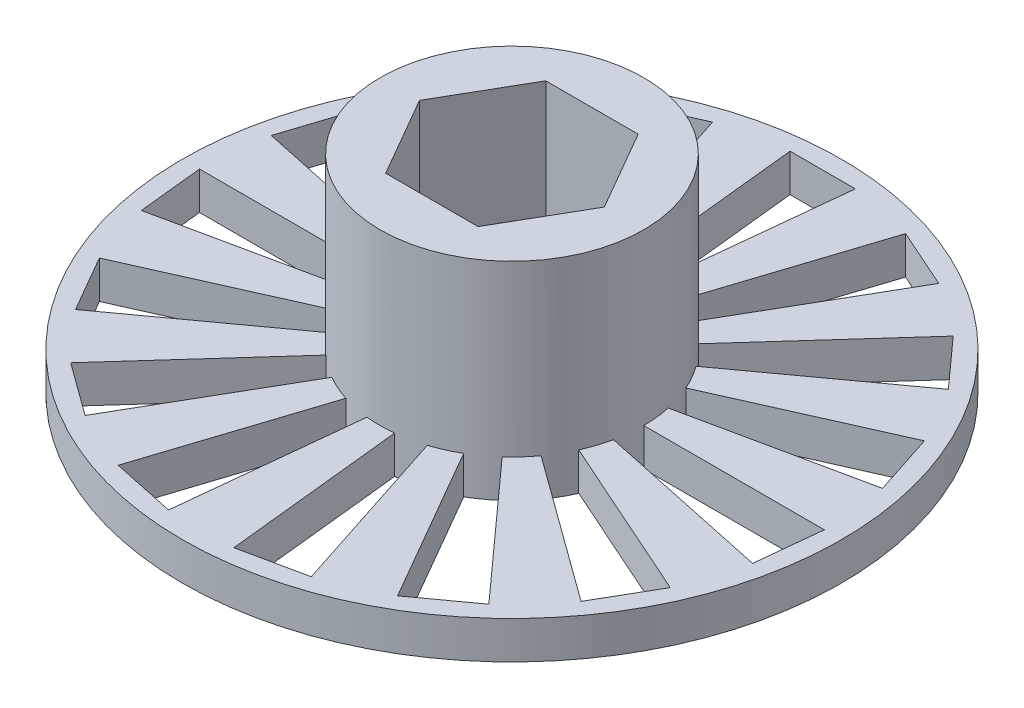
SolidWorks part; units mm, degrees
ref_plane "Front Plane" through (0, 0, 0) normal (0, 0, 1) x (1, 0, 0)
ref_plane "Top Plane" through (0, 0, 0) normal (0, 1, 0) x (1, 0, 0)
ref_plane "Right Plane" through (0, 0, 0) normal (1, 0, 0) x (0, 0, -1)
sketch "Sketch1" plane through (0, 0, 0) normal (0, 1, 0) x (1, 0, 0)
  line L0 (0, 0) -> (0, 50000) construction
  line L1 (0, 0) -> (5226.4232, 49726.0948) construction
  line L2 (0, 0) -> (-5226.4232, 49726.0948) construction
  line L3 (3.2679, 5.6602) -> (8.2954, 14.3681)
  line L4 (5.1269, 15.7789) -> (8.2954, 14.3681)
  line L5 (2.0197, 6.2159) -> (5.1269, 15.7789)
  line L6 (2.0197, 6.2159) -> (3.2679, 5.6602)
  line L7 (0.6832, 6.5) -> (1.7342, 16.5)
  line L8 (-0.6832, 6.5) -> (-1.7342, 16.5)
  line L9 (5.2876, 3.8416) -> (13.4223, 9.7519)
  line L10 (11.1015, 12.3294) -> (13.4223, 9.7519)
  line L11 (-1.7342, 16.5) -> (1.7342, 16.5)
  line L12 (-0.6832, 6.5) -> (0.6832, 6.5)
  line L13 (4.3733, 4.857) -> (11.1015, 12.3294)
  line L14 (4.3733, 4.857) -> (5.2876, 3.8416)
  line L15 (6.393, 1.3589) -> (16.2283, 3.4494)
  line L16 (15.1565, 6.7481) -> (16.2283, 3.4494)
  line L17 (5.9708, 2.6584) -> (15.1565, 6.7481)
  line L18 (5.9708, 2.6584) -> (6.393, 1.3589)
  line L19 (6.393, -1.3589) -> (16.2283, -3.4494)
  line L20 (16.5909, 0) -> (16.2283, -3.4494)
  line L21 (6.5358, 0) -> (16.5909, 0)
  line L22 (6.5358, 0) -> (6.393, -1.3589)
  line L23 (5.2876, -3.8416) -> (13.4223, -9.7519)
  line L24 (15.1565, -6.7481) -> (13.4223, -9.7519)
  line L25 (5.9708, -2.6584) -> (15.1565, -6.7481)
  line L26 (5.9708, -2.6584) -> (5.2876, -3.8416)
  line L27 (3.2679, -5.6602) -> (8.2954, -14.3681)
  line L28 (11.1015, -12.3294) -> (8.2954, -14.3681)
  line L29 (4.3733, -4.857) -> (11.1015, -12.3294)
  line L30 (4.3733, -4.857) -> (3.2679, -5.6602)
  line L31 (0.6832, -6.5) -> (1.7342, -16.5)
  line L32 (5.1269, -15.7789) -> (1.7342, -16.5)
  line L33 (2.0197, -6.2159) -> (5.1269, -15.7789)
  line L34 (2.0197, -6.2159) -> (0.6832, -6.5)
  line L35 (-2.0197, -6.2159) -> (-5.1269, -15.7789)
  line L36 (-1.7342, -16.5) -> (-5.1269, -15.7789)
  line L37 (-0.6832, -6.5) -> (-1.7342, -16.5)
  line L38 (-0.6832, -6.5) -> (-2.0197, -6.2159)
  line L39 (-4.3733, -4.857) -> (-11.1015, -12.3294)
  line L40 (-8.2954, -14.3681) -> (-11.1015, -12.3294)
  line L41 (-3.2679, -5.6602) -> (-8.2954, -14.3681)
  line L42 (-3.2679, -5.6602) -> (-4.3733, -4.857)
  line L43 (-5.9708, -2.6584) -> (-15.1565, -6.7481)
  line L44 (-13.4223, -9.7519) -> (-15.1565, -6.7481)
  line L45 (-5.2876, -3.8416) -> (-13.4223, -9.7519)
  line L46 (-5.2876, -3.8416) -> (-5.9708, -2.6584)
  line L47 (-6.5358, 0) -> (-16.5909, 0)
  line L48 (-16.2283, -3.4494) -> (-16.5909, 0)
  line L49 (-6.393, -1.3589) -> (-16.2283, -3.4494)
  line L50 (-6.393, -1.3589) -> (-6.5358, 0)
  line L51 (-5.9708, 2.6584) -> (-15.1565, 6.7481)
  line L52 (-16.2283, 3.4494) -> (-15.1565, 6.7481)
  line L53 (-6.393, 1.3589) -> (-16.2283, 3.4494)
  line L54 (-6.393, 1.3589) -> (-5.9708, 2.6584)
  line L55 (-4.3733, 4.857) -> (-11.1015, 12.3294)
  line L56 (-13.4223, 9.7519) -> (-11.1015, 12.3294)
  line L57 (-5.2876, 3.8416) -> (-13.4223, 9.7519)
  line L58 (-5.2876, 3.8416) -> (-4.3733, 4.857)
  line L59 (-2.0197, 6.2159) -> (-5.1269, 15.7789)
  line L60 (-8.2954, 14.3681) -> (-5.1269, 15.7789)
  line L61 (-3.2679, 5.6602) -> (-8.2954, 14.3681)
  line L62 (-3.2679, 5.6602) -> (-2.0197, 6.2159)
  line L64 (4.9075, 0) -> (2.4537, 4.25)
  line L65 (2.4537, 4.25) -> (-2.4537, 4.25)
  line L66 (-2.4537, 4.25) -> (-4.9075, 0)
  line L67 (-4.9075, 0) -> (-2.4537, -4.25)
  line L68 (-2.4537, -4.25) -> (2.4537, -4.25)
  line L69 (2.4537, -4.25) -> (4.9075, 0)
  circle A0 centre (0, 0) radius 17.5
  circle A1 centre (0, 0) radius 4.25 construction
  point P7 (0, 16.5)
  point P11 (0, 17.5)
  point P68 (0.0003, -0.0005)
  point P75 (0, 0)
  dimension "D1" = 35
  dimension "D2" = 6
  dimension "D3" = 6
  dimension "D4" = 6.5
  dimension "D5" = 1
  dimension "D6" = 15
  dimension "D7" = 8.5
extrude "Boss-Extrude1" add sketch "Sketch1" along normal blind 1 and the other way blind 1
sketch "Sketch2" plane through (0, 0, 0) normal (0, 1, 0) x (1, 0, 0)
  line L1 (4.9075, 0) -> (2.4537, 4.25)
  line L2 (2.4537, 4.25) -> (-2.4537, 4.25)
  line L3 (-2.4537, 4.25) -> (-4.9075, 0)
  line L4 (-4.9075, 0) -> (-2.4537, -4.25)
  line L5 (-2.4537, -4.25) -> (2.4537, -4.25)
  line L6 (2.4537, -4.25) -> (4.9075, 0)
  circle A0 centre (0, 0) radius 7
  circle A1 centre (0, 0) radius 4.25 construction
  dimension "D1" = 8.5
  dimension "D2" = 14
extrude "Boss-Extrude2" add sketch "Sketch2" along normal blind 10 and the other way up to surface (1 mm away) other way up to face at (-4.6775, -1, -10.5058)
